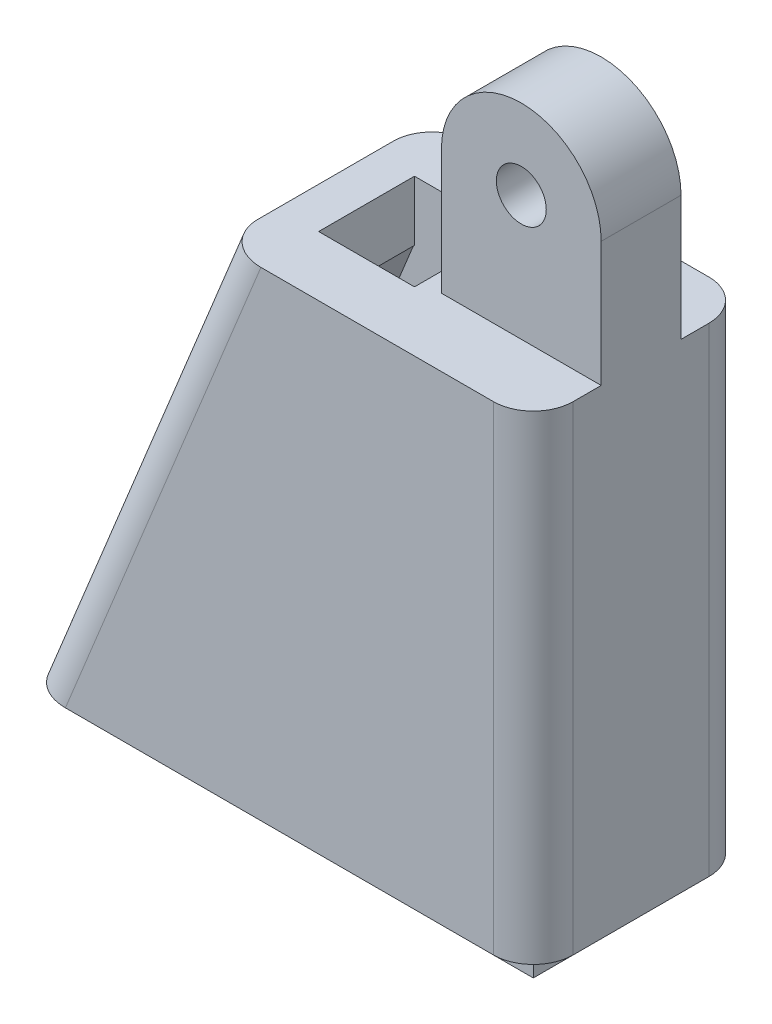
SolidWorks part; units mm, degrees
ref_plane "Front Plane" through (0, 0, 0) normal (0, 0, 1) x (1, 0, 0)
ref_plane "Top Plane" through (0, 0, 0) normal (0, 1, 0) x (1, 0, 0)
ref_plane "Right Plane" through (0, 0, 0) normal (1, 0, 0) x (0, 0, -1)
sketch "Sketch1" plane through (0, 0, 0) normal (0, 1, 0) x (1, 0, 0)
  line L1 (-13, -5.4) -> (13, -5.4)
  line L2 (-13, -5.4) -> (-13, 5.4)
  line L3 (-13, 5.4) -> (13, 5.4)
  line L4 (13, -5.4) -> (13, 5.4)
  line L5 (-13, -5.4) -> (13, 5.4) construction
  line L6 (-13, 5.4) -> (13, -5.4) construction
  point P0 (0, 0)
  dimension "D1" = 10.8
  dimension "D2" = 26
extrude "Boss-Extrude1" add sketch "Sketch1" along normal blind 25
sketch "Sketch2" plane through (0, 25, 0) normal (0, 1, 0) x (1, 0, 0)
  line L0 (13, -5.4) -> (13, 5.4) construction
  line L1 (13, 2) -> (5, 2)
  line L2 (13, 2) -> (13, -2)
  line L3 (13, -2) -> (5, -2)
  line L4 (5, 2) -> (5, -2)
  point P6 (5, 0)
  point P7 (13, 0)
  dimension "D1" = 8
  dimension "D2" = 4
extrude "Boss-Extrude2" add sketch "Sketch2" along normal blind 10.25
sketch "Sketch3" plane through (0, 0, 2) normal (0, 0, 1) x (1, 0, 0)
  line L0 (5, 35.25) -> (5, 25) construction
  line L1 (13, 35.25) -> (13, 25) construction
  line L2 (5, 35.25) -> (13, 35.25) construction
  line L3 (5, 31.25) -> (5, 37.25)
  line L4 (5, 37.25) -> (13, 37.25)
  line L5 (13, 37.25) -> (13, 31.25)
  arc A0 (5, 31.25) -> (13, 31.25) centre (9, 31.25) cw
  circle A1 centre (9, 31.25) radius 1.25
  dimension "D1" = 2.5
  dimension "D2" = 6
extrude "Cut-Extrude1" cut sketch "Sketch3" against normal blind 10.25
sketch "Sketch4" plane through (0, 0, 5.4) normal (0, 0, 1) x (1, 0, 0)
  line L0 (-13, 0) -> (-2.8, 25)
  line L1 (-13, 25) -> (13, 25) construction
  line L2 (-2.8, 25) -> (-13, 25)
  line L3 (-13, 25) -> (-13, 0)
  point P5 (5, 25)
  dimension "D1" = 7.8
extrude "Cut-Extrude2" cut sketch "Sketch4" against normal through all
shell "Shell1" thickness 3 removed face at (3.25, 0, -1.35)
sketch "Sketch5" plane through (0, 25, 0) normal (0, 1, 0) x (1, 0, 0)
  line L0 (5, 2) -> (5, -2) construction
  line L1 (4.05, 2.4) -> (-0.75, 2.4)
  line L2 (4.05, 2.4) -> (4.05, -2.4)
  line L3 (4.05, -2.4) -> (-0.75, -2.4)
  line L4 (-0.75, 2.4) -> (-0.75, -2.4)
  point P4 (4.05, 0)
  point P5 (5, 0)
  dimension "D1" = 4.8
  dimension "D2" = 0.95
extrude "Cut-Extrude3" cut sketch "Sketch5" against normal blind 10.25
sketch "Sketch6" plane through (13, 0, 0) normal (1, 0, 0) x (0, 0, -1)
  line L1 (-5.4, 0) -> (-4.4, 0)
  line L2 (-5.4, 0) -> (-5.4, 1)
  line L3 (-5.4, 1) -> (-4.4, 1)
  line L4 (-4.4, 0) -> (-4.4, 1)
  line L5 (5.4, 0) -> (4.4, 0)
  line L6 (5.4, 0) -> (5.4, 1)
  line L7 (5.4, 1) -> (4.4, 1)
  line L8 (4.4, 0) -> (4.4, 1)
  dimension "D1" = 1
sketch "Sketch7" plane through (0, 0, -5.4) normal (0, 0, -1) x (-1, 0, 0)
  line L1 (-13, 0) -> (-12, 0)
  line L2 (-13, 0) -> (-13, 1)
  line L3 (-13, 1) -> (-12, 1)
  line L4 (-12, 0) -> (-12, 1)
  line L5 (13, 0) -> (12, 0)
  line L6 (13, 0) -> (13, 1)
  line L7 (13, 1) -> (12, 1)
  line L8 (12, 0) -> (12, 1)
  dimension "D1" = 1
extrude "Cut-Extrude4" cut sketch "Sketch6" against normal through all
extrude "Cut-Extrude5" cut sketch "Sketch7" against normal blind 10.25
fillet "Fillet1" radius 2 4 edges at (13, 13, 5.4) (-7.696, 13, 5.4) (13, 13, -5.4)
fillet "Fillet2" radius 2 3 edges at (-12, 0.5, 4.4) (-12, 0.5, -4.4) (12, 0.5, -4.4)
